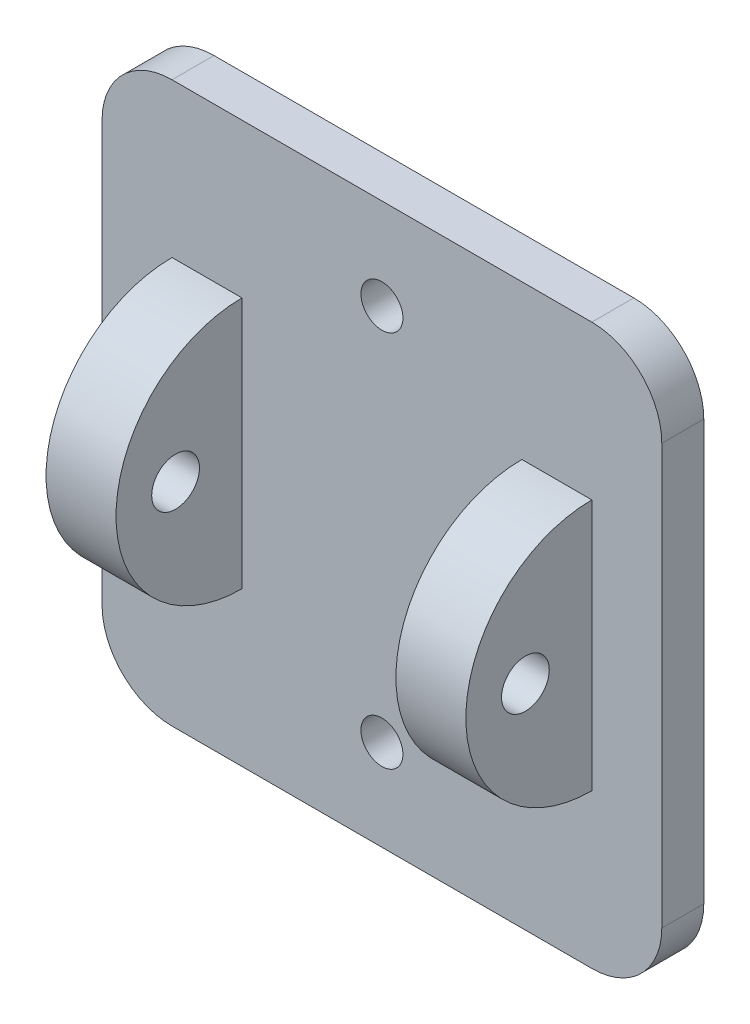
SolidWorks part; units mm, degrees
ref_plane "Alzado" through (0, 0, 0) normal (0, 0, 1) x (1, 0, 0)
ref_plane "Planta" through (0, 0, 0) normal (0, 1, 0) x (1, 0, 0)
ref_plane "Vista lateral" through (0, 0, 0) normal (1, 0, 0) x (0, 0, -1)
sketch "Croquis1" plane through (0, 0, 0) normal (0, 0, 1) x (1, 0, 0)
  line L0 (7.3124, 13.7981) -> (7.3124, -26.2019) construction
  line L1 (-7.6876, 13.7981) -> (22.3124, 13.7981)
  line L2 (-12.6876, 8.7981) -> (-12.6876, -21.2019)
  line L3 (-7.6876, -26.2019) -> (22.3124, -26.2019)
  line L4 (27.3124, 8.7981) -> (27.3124, -21.2019)
  arc A0 (-12.6876, -21.2019) -> (-7.6876, -26.2019) centre (-7.6876, -21.2019) ccw
  arc A1 (22.3124, -26.2019) -> (27.3124, -21.2019) centre (22.3124, -21.2019) ccw
  arc A2 (22.3124, 13.7981) -> (27.3124, 8.7981) centre (22.3124, 8.7981) cw
  arc A3 (-7.6876, 13.7981) -> (-12.6876, 8.7981) centre (-7.6876, 8.7981) ccw
  circle A4 centre (7.3124, 7.2981) radius 1.5
  circle A5 centre (7.3124, -19.7019) radius 1.5
  point P8 (27.3124, -26.2019)
  point P11 (27.3124, 13.7981)
  point P14 (-12.6876, 13.7981)
  dimension "D3" = 5
  dimension "D4" = 3
  dimension "D1" = 40
  dimension "D2" = 40
  dimension "D5" = 27
  dimension "D6" = 6.5
extrude "Saliente-Extruir1" add sketch "Croquis1" along normal blind 3
sketch "Croquis2" plane through (0, 0, 0) normal (0, 0, 1) x (1, 0, 0)
  line L0 (7.3124, 13.7981) -> (7.3124, -26.2019) construction
  line L1 (-7.6876, 2.7981) -> (-2.6876, 2.7981)
  line L2 (-7.6876, 2.7981) -> (-7.6876, -15.2019)
  line L3 (-7.6876, -15.2019) -> (-2.6876, -15.2019)
  line L4 (-2.6876, 2.7981) -> (-2.6876, -15.2019)
  line L5 (22.3124, 13.7981) -> (-7.6876, 13.7981) construction
  line L6 (-7.6876, -26.2019) -> (22.3124, -26.2019) construction
  line L7 (-12.6876, 8.7981) -> (-12.6876, -21.2019) construction
  line L8 (22.3124, -15.2019) -> (17.3124, -15.2019)
  line L9 (22.3124, 2.7981) -> (22.3124, -15.2019)
  line L10 (17.3124, 2.7981) -> (17.3124, -15.2019)
  line L11 (22.3124, 2.7981) -> (17.3124, 2.7981)
  dimension "D1" = 5
  dimension "D2" = 18
  dimension "D3" = 11
  dimension "D4" = 5
extrude "Saliente-Extruir2" add sketch "Croquis2" along normal blind 9 from surface starting at face at (8.8124, 7.2981, 3)
fillet "Redondeo6" 2 edges at (-5.1876, -15.2019, 12) (-5.1876, 2.7981, 12) type full round first side face at (-5.1876, -15.2019, 7.5) second side face at (-5.1876, 2.7981, 7.5) middle face at (-5.1876, -6.2019, 12)
fillet "Redondeo7" 2 edges at (19.8124, -15.2019, 12) (19.8124, 2.7981, 12) type full round first side face at (19.8124, -15.2019, 7.5) second side face at (19.8124, 2.7981, 7.5) middle face at (19.8124, -6.2019, 12)
sketch "Croquis3" plane through (-7.6876, 0, 0) normal (-1, 0, 0) x (0, 0, 1)
  line L0 (3, -6.2019) -> (7.7463, -6.2019) construction
  line L1 (3, 8.7981) -> (3, -21.2019) construction
  circle A0 centre (7.7463, -6.2019) radius 1.7056
  dimension "D1" = 4.7463
extrude "Cortar-Extruir1" cut sketch "Croquis3" against normal up to surface (30 mm away) contours A0 up to face at (22.3124, -6.2019, 7.5)
